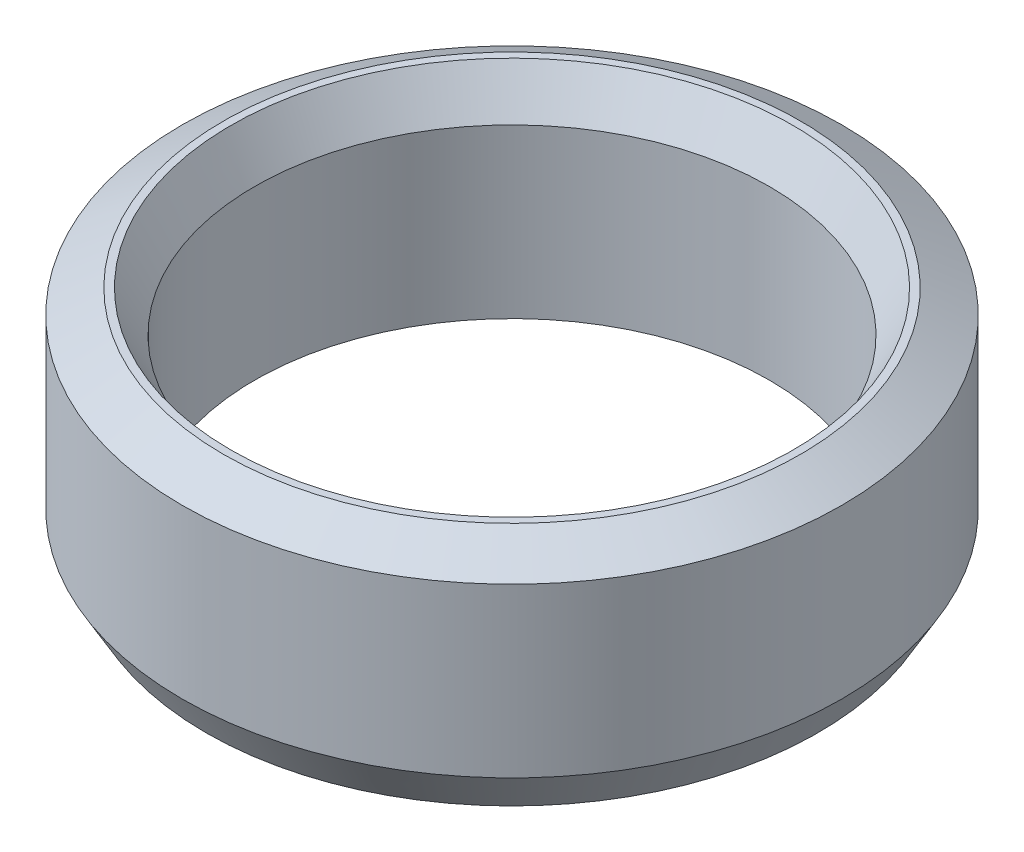
SolidWorks part; units mm, degrees
ref_plane "Front Plane" through (0, 0, 0) normal (0, 0, 1) x (1, 0, 0)
ref_plane "Top Plane" through (0, 0, 0) normal (0, 1, 0) x (1, 0, 0)
ref_plane "Right Plane" through (0, 0, 0) normal (1, 0, 0) x (0, 0, -1)
sketch "Sketch1" plane through (0, 0, 0) normal (0, 1, 0) x (1, 0, 0)
  circle A0 centre (0, 0) radius 40
  dimension "SLEEVE_OD" = 80
extrude "Boss-Extrude1" add sketch "Sketch1" along normal blind 28.2076
sketch "Sketch2" plane through (0, 0, 0) normal (0, 1, 0) x (1, 0, 0)
  circle A0 centre (0, 0) radius 31.2313
  dimension "BORE_D" = 62.4626
extrude "Cut-Extrude1" cut sketch "Sketch2" along normal through all
chamfer "Chamfer1" distance 2.8765 angle 60 4 edges at (0, 28.2076, 31.2313) (0, 0, 31.2313) (0, 0, 40) (0, 28.2076, 40) first distance on face at (0, 28.2076, 31.2313) first distance on face at (0, 0, 31.2313) first distance on face at (0, 28.2076, 40)
